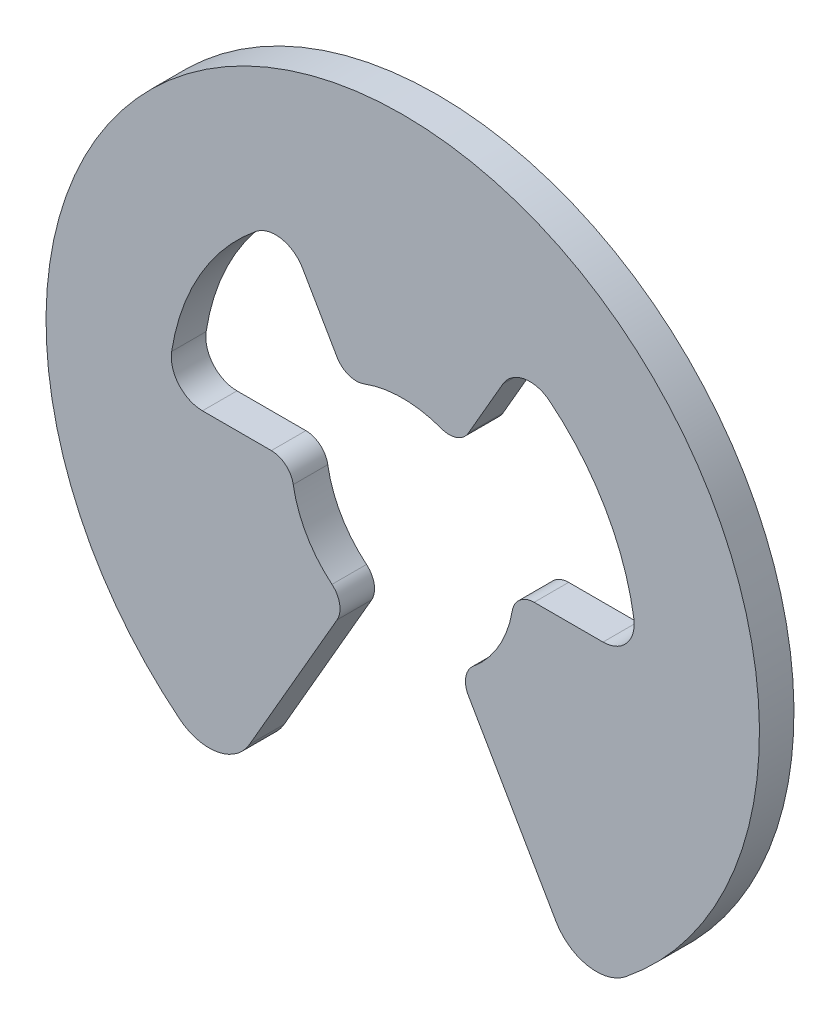
SolidWorks part; units mm, degrees
ref_plane "Front Plane" through (0, 0, 0) normal (0, 0, 1) x (1, 0, 0)
ref_plane "Top Plane" through (0, 0, 0) normal (0, 1, 0) x (1, 0, 0)
ref_plane "Right Plane" through (0, 0, 0) normal (1, 0, 0) x (0, 0, -1)
sketch "Sketch1" plane through (0, 0, 0) normal (0, 0, 1) x (1, 0, 0)
  line L0 (-1.6908, -2.9285) -> (-0.725, -1.2558)
  line L1 (-1.4501, 0) -> (-2.2105, 0)
  line L2 (-1.1052, 1.9143) -> (-0.725, 1.2558)
  line L3 (0.725, 1.2558) -> (1.1052, 1.9143)
  line L4 (2.2105, 0) -> (1.4501, 0)
  line L5 (0.725, -1.2558) -> (1.6908, -2.9285)
  arc A0 (2.4605, -3.0734) -> (-2.4605, -3.0734) centre (0, 0) ccw
  arc A1 (-2.4605, -3.0734) -> (-1.6908, -2.9285) centre (-2.1379, -2.6704) ccw
  arc A2 (-0.725, -1.2558) -> (-0.7811, -0.9444) centre (-0.9373, -1.1333) ccw
  arc A3 (-0.7811, -0.9444) -> (-1.2084, -0.2043) centre (0, 0) cw
  arc A4 (-1.2084, -0.2043) -> (-1.4501, 0) centre (-1.4501, -0.2451) ccw
  arc A5 (-2.2105, 0) -> (-2.5505, 0.3971) centre (-2.2105, 0.3442) cw
  arc A6 (-2.5505, 0.3971) -> (-1.6192, 2.0103) centre (0, 0) cw
  arc A7 (-1.6192, 2.0103) -> (-1.1052, 1.9143) centre (-1.4033, 1.7422) cw
  arc A8 (-0.725, 1.2558) -> (-0.4273, 1.1486) centre (-0.5128, 1.3784) ccw
  arc A9 (-0.4273, 1.1486) -> (0.4273, 1.1486) centre (0, 0) cw
  arc A10 (0.4273, 1.1486) -> (0.725, 1.2558) centre (0.5128, 1.3784) ccw
  arc A11 (1.1052, 1.9143) -> (1.6192, 2.0103) centre (1.4033, 1.7422) cw
  arc A12 (1.6192, 2.0103) -> (2.5505, 0.3971) centre (0, 0) cw
  arc A13 (2.5505, 0.3971) -> (2.2105, 0) centre (2.2105, 0.3442) cw
  arc A14 (1.4501, 0) -> (1.2084, -0.2043) centre (1.4501, -0.2451) ccw
  arc A15 (1.2084, -0.2043) -> (0.7811, -0.9444) centre (0, 0) cw
  arc A16 (0.7811, -0.9444) -> (0.725, -1.2558) centre (0.9373, -1.1333) ccw
  arc A17 (1.6908, -2.9285) -> (2.4605, -3.0734) centre (2.1379, -2.6704) ccw
extrude "Boss-Extrude1" add sketch "Sketch1" against normal blind 0.1905 and the other way blind 0.1905
ref_plane "RR XY" through (0, 0, 0) normal (0, 0, 1) x (1, 0, 0)
ref_plane "RR XZ" through (0, 0, 0) normal (0, -1, 0) x (-1, 0, 0)
ref_plane "RR YZ" through (0, 0, 0) normal (1, 0, 0) x (0, 0, -1)
ref_axis "RR X" through (-80.9, 0, 0) along (1, 0, 0)
ref_axis "RR Y" through (0, -50, 0) along (0, 1, 0)
ref_axis "RR Z" through (0, 0, 80.9) along (0, 0, -1)
sketch3d "RR"
  point P0 (0, 0, 0)
